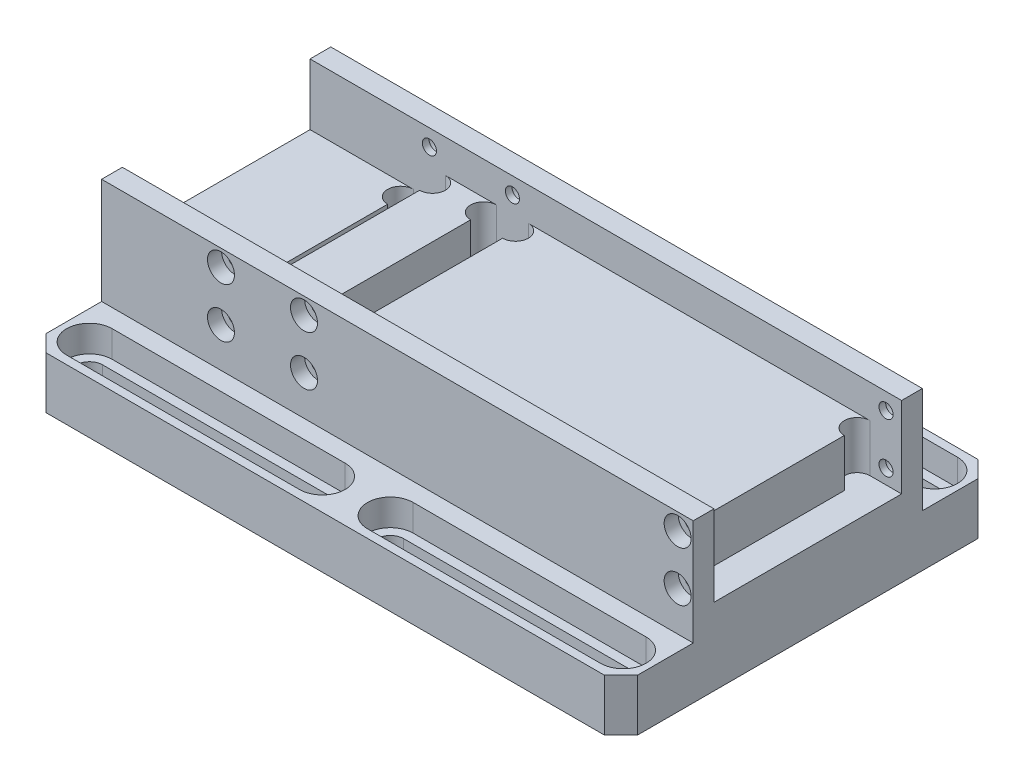
SolidWorks part; units mm, degrees
material "7075-T6 (SN)"
ref_plane "Front Plane" through (0, 0, 0) normal (0, 0, 1) x (1, 0, 0)
ref_plane "Top Plane" through (0, 0, 0) normal (0, 1, 0) x (1, 0, 0)
ref_plane "Right Plane" through (0, 0, 0) normal (1, 0, 0) x (0, 0, -1)
sketch "Sketch1" plane through (0, 0, 0) normal (0, 1, 0) x (1, 0, 0)
  line L1 (-71.25, -45) -> (71.25, -45)
  line L2 (-71.25, -45) -> (-71.25, 45)
  line L3 (-71.25, 45) -> (71.25, 45)
  line L4 (71.25, -45) -> (71.25, 45)
  line L5 (-71.25, -45) -> (71.25, 45) construction
  line L6 (-71.25, 45) -> (71.25, -45) construction
  point P0 (0, 0)
  dimension "D1" = 90
  dimension "D2" = 142.5
extrude "Boss-Extrude1" add sketch "Sketch1" along normal blind 12.5 contours L1 L4 L3 L2 region at (0, 0, 0)
chamfer "Chamfer1" distance 4 angle 45 4 edges at (-71.25, 6.25, -45) (71.25, 6.25, -45) (71.25, 6.25, 45) (-71.25, 6.25, 45)
sketch "Sketch3" plane through (0, 12.5, 0) normal (0, 1, 0) x (1, 0, 0)
  line L0 (71.25, -41) -> (71.25, 41) construction
  line L1 (-71.25, -27.6) -> (71.25, -27.6)
  line L2 (-71.25, -27.6) -> (-71.25, 27.6)
  line L3 (-71.25, 27.6) -> (71.25, 27.6)
  line L4 (71.25, -27.6) -> (71.25, 27.6)
  line L5 (-71.25, -27.6) -> (71.25, 27.6) construction
  line L6 (-71.25, 27.6) -> (71.25, -27.6) construction
  line L8 (-67.25, 45) -> (67.25, 45) construction
  point P0 (0, 0)
  dimension "D1" = 17.4
extrude "Boss-Extrude2" add sketch "Sketch3" along normal blind 25.5
sketch "Sketch7" plane through (0, 38, 0) normal (0, 1, 0) x (1, 0, 0)
  line L0 (71.25, -27.6) -> (71.25, 27.6) construction
  line L1 (-71.25, -22.6) -> (71.25, -22.6)
  line L2 (-71.25, -22.6) -> (-71.25, 22.6)
  line L3 (-71.25, 22.6) -> (71.25, 22.6)
  line L4 (71.25, -22.6) -> (71.25, 22.6)
  line L5 (-71.25, -22.6) -> (71.25, 22.6) construction
  line L6 (-71.25, 22.6) -> (71.25, -22.6) construction
  point P0 (0, 0)
  dimension "D1" = 45.2
extrude "Cut-Extrude4" cut sketch "Sketch7" against normal blind 8
sketch "Sketch8" plane through (0, 30, 0) normal (0, 1, 0) x (1, 0, 0)
  line L0 (71.25, 22.6) -> (-71.25, 22.6) construction
  line L1 (-46.35, -22.6) -> (-38.65, -22.6)
  line L2 (-46.35, -22.6) -> (-46.35, 22.6)
  line L3 (-46.35, 22.6) -> (-38.65, 22.6)
  line L4 (-38.65, -22.6) -> (-38.65, 22.6)
  line L5 (-46.35, -22.6) -> (-38.65, 22.6) construction
  line L6 (-46.35, 22.6) -> (-38.65, -22.6) construction
  line L7 (71.25, -22.6) -> (71.25, 22.6) construction
  line L8 (-71.25, -22.6) -> (71.25, -22.6) construction
  line L9 (-46.35, 19.5) -> (-38.65, 19.5) construction
  line L10 (-46.35, 22.6) -> (-38.65, 22.6)
  line L11 (-46.35, 16.4) -> (-38.65, 16.4)
  line L12 (-46.35, -19.5) -> (-38.65, -19.5) construction
  line L13 (-46.35, -16.4) -> (-38.65, -16.4)
  line L14 (-46.35, -22.6) -> (-38.65, -22.6)
  line L15 (-71.25, -22.6) -> (71.25, -22.6) construction
  line L16 (71.25, 22.6) -> (-71.25, 22.6) construction
  line L17 (-71.25, 22.6) -> (-71.25, -22.6) construction
  line L18 (-26.35, 19.5) -> (-18.65, 19.5) construction
  line L19 (-26.35, -22.6) -> (-18.65, -22.6)
  line L20 (-26.35, -22.6) -> (-26.35, 22.6)
  line L21 (-26.35, 22.6) -> (-18.65, 22.6)
  line L22 (-18.65, -22.6) -> (-18.65, 22.6)
  line L23 (-26.35, -22.6) -> (-18.65, 22.6) construction
  line L24 (-26.35, 22.6) -> (-18.65, -22.6) construction
  line L25 (63.65, -22.6) -> (71.35, -22.6)
  line L26 (63.65, -22.6) -> (63.65, 22.6)
  line L27 (63.65, 22.6) -> (71.35, 22.6)
  line L28 (71.35, -22.6) -> (71.35, 22.6)
  line L29 (63.65, -22.6) -> (71.35, 22.6) construction
  line L30 (63.65, 22.6) -> (71.35, -22.6) construction
  line L31 (-26.35, 22.6) -> (-18.65, 22.6)
  line L32 (-26.35, 16.4) -> (-18.65, 16.4)
  line L33 (-26.35, -19.5) -> (-18.65, -19.5) construction
  line L34 (-26.35, -16.4) -> (-18.65, -16.4)
  line L35 (-26.35, -22.6) -> (-18.65, -22.6)
  line L36 (63.65, 19.5) -> (71.35, 19.5) construction
  line L37 (63.65, 22.6) -> (71.35, 22.6)
  line L38 (63.65, 16.4) -> (71.35, 16.4)
  line L39 (63.65, -19.5) -> (71.35, -19.5) construction
  line L40 (63.65, -16.4) -> (71.35, -16.4)
  line L41 (63.65, -22.6) -> (71.35, -22.6)
  arc A0 (-46.35, 22.6) -> (-46.35, 16.4) centre (-46.35, 19.5) ccw
  arc A1 (-38.65, 16.4) -> (-38.65, 22.6) centre (-38.65, 19.5) ccw
  arc A2 (-46.35, -16.4) -> (-46.35, -22.6) centre (-46.35, -19.5) ccw
  arc A3 (-38.65, -22.6) -> (-38.65, -16.4) centre (-38.65, -19.5) ccw
  arc A4 (-26.35, 22.6) -> (-26.35, 16.4) centre (-26.35, 19.5) ccw
  arc A5 (-18.65, 16.4) -> (-18.65, 22.6) centre (-18.65, 19.5) ccw
  arc A6 (-26.35, -16.4) -> (-26.35, -22.6) centre (-26.35, -19.5) ccw
  arc A7 (-18.65, -22.6) -> (-18.65, -16.4) centre (-18.65, -19.5) ccw
  arc A8 (63.65, 22.6) -> (63.65, 16.4) centre (63.65, 19.5) ccw
  arc A9 (71.35, 16.4) -> (71.35, 22.6) centre (71.35, 19.5) ccw
  arc A10 (63.65, -16.4) -> (63.65, -22.6) centre (63.65, -19.5) ccw
  arc A11 (71.35, -22.6) -> (71.35, -16.4) centre (71.35, -19.5) ccw
  point P0 (-42.5, 0)
  point P10 (-42.5, 19.5)
  point P19 (-42.5, -19.5)
  point P29 (67.5, 0)
  point P32 (-22.5, 0)
  point P41 (-22.5, 19.5)
  point P49 (-22.5, -19.5)
  point P56 (67.5, 19.5)
  point P63 (67.5, -19.5)
  line M10 (71.25, 22.6) -> (-71.25, 22.6)
  line M12 (-71.25, -22.6) -> (71.25, -22.6)
  dimension "D1" = 28.75
  dimension "D2" = 7.7
  dimension "D3" = 6.2
  dimension "D4" = 20
  dimension "D5" = 3.75
extrude "Cut-Extrude5" cut sketch "Sketch8" against normal blind 11.5 contours L2 A0 | L4 A1 | L2 L13 L4 L11 | L2 L11 L4 M10 | L2 A2 | L4 A3 | L13 L2 L4 M12 | L4 L3 L2 L1 | L20 L19 L22 L21 | L32 A5 L31 A4 | L35 A7 L34 A6 | L26 L25 L28 L27 | L38 A9 L37 A8 | L41 A11 L40 A10 region at (-42.5, 30, 19.5) region at (-47.6657, 30, 19.5) region at (-37.3343, 30, 19.5) region at (-42.5, 30, 0) region at (-47.6657, 30, -19.5) region at (-42.5, 30, -19.5) region at (-37.3343, 30, -19.5)
sketch "Sketch9" plane through (0, 30, 0) normal (0, 1, 0) x (1, 0, 0)
  line L1 (-71.25, 22.6) -> (-46.35, 22.6)
  line L2 (-71.25, 22.6) -> (-71.25, -22.6)
  line L3 (-71.25, -22.6) -> (-46.35, -22.6)
  line L4 (-46.35, 22.6) -> (-46.35, -22.6)
extrude "Cut-Extrude6" cut sketch "Sketch9" against normal blind 6.75
hole_wizard "CBORE for M3 Hex Socket Head Cap Screw1" positions "Sketch10" profile "Sketch11" counterbore size "M3" standard "DIN" end condition up to next
sketch "Sketch10" plane through (0, 0, 27.6) normal (0, 0, 1) x (1, 0, 0)
  line L0 (71.25, 38) -> (71.25, 12.5) construction
  line L1 (-71.25, 38) -> (71.25, 38) construction
  line L2 (-71.25, 38) -> (-71.25, 12.5) construction
  point P0 (67.5, 34)
  point P2 (67.5, 22)
  point P16 (-22.5, 34)
  point P18 (-22.5, 22)
  point P20 (-42.5, 22)
  point P22 (-42.5, 34)
  dimension "D1" = 3.75
  dimension "D2" = 4
  dimension "D3" = 12
  dimension "D4" = 20
  dimension "D5" = 28.75
sketch "Sketch11" plane through (67.5, 34, 27.6) normal (1, 0, 0) x (0, -1, 0)
  line L0 (0, 0) -> (0, 55.2)
  line L1 (0, 55.2) -> (1.7, 55.2)
  line L3 (1.7, 55.2) -> (1.7, 3.4)
  line L4 (1.7, 3.4) -> (3.25, 3.4)
  line L5 (3.25, 3.4) -> (3.25, 0)
  line L7 (3.25, 0) -> (0, 0)
  line L11 (0, -6.35) -> (0, 107.95) construction
  dimension "Thru Hole Dia." = 3.4
  dimension "Thru Hole Depth" = 55.2
  dimension "C'Bore Dia." = 6.5
  dimension "C'Bore Depth" = 3.4
mirror "Mirror1" about plane through (0, 0, 0) normal (0, 0, 1) of "CBORE for M3 Hex Socket Head Cap Screw1"
hole_wizard "CBORE SLOT for M6 Hex Socket Head Cap Screw1" positions "Sketch12" profile "Sketch13" size "M6" standard "DIN" slot yes end condition up to next
sketch "Sketch12" plane through (0, 12.5, 0) normal (0, 1, 0) x (1, 0, 0)
  line L0 (-67.5, -37.5) -> (-5, -37.5) construction
  line L4 (71.25, -41) -> (71.25, -27.6) construction
  line L5 (-71.25, 27.6) -> (-71.25, 41) construction
  point P6 (-36.25, -37.5)
  point P10 (-36.25, 37.5)
  point P12 (36.25, 37.5)
  point P14 (36.25, -37.5)
  dimension "D1" = 62.5
  dimension "D2" = 75
  dimension "D3" = 35
  dimension "D4" = 35
  dimension "D5" = 37.5
sketch "Sketch13" plane through (-36.25, 12.5, 37.5) normal (1, 0, 0) x (0, 0, 1)
  line L0 (0, 0) -> (0, 12.5)
  line L1 (0, 12.5) -> (3.2, 12.5)
  line L3 (3.2, 12.5) -> (3.2, 6.4)
  line L4 (3.2, 6.4) -> (5.5, 6.4)
  line L5 (5.5, 6.4) -> (5.5, 0)
  line L7 (5.5, 0) -> (0, 0)
  line L11 (0, -6.35) -> (0, 107.95) construction
  dimension "Thru Hole Dia." = 6.4
  dimension "Thru Hole Depth" = 12.5
  dimension "C'Bore Dia." = 11
  dimension "C'Bore Depth" = 6.4
